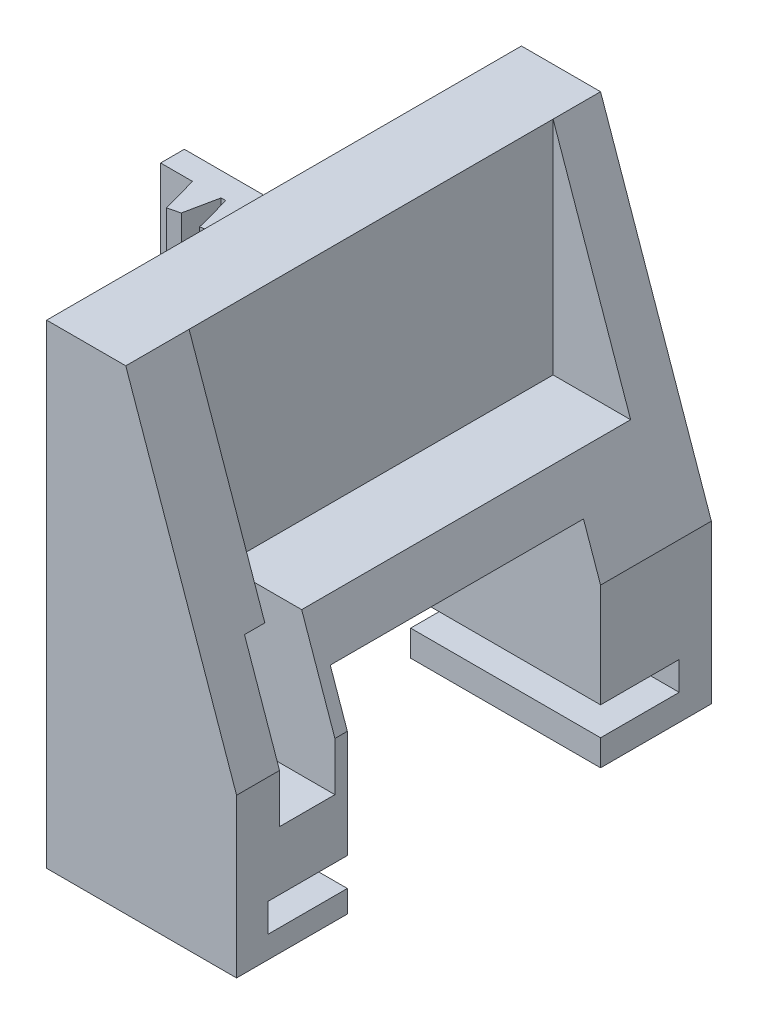
SolidWorks part; units mm, degrees
ref_plane "Front Plane" through (0, 0, 0) normal (0, 0, 1) x (1, 0, 0)
ref_plane "Top Plane" through (0, 0, 0) normal (0, 1, 0) x (1, 0, 0)
ref_plane "Right Plane" through (0, 0, 0) normal (1, 0, 0) x (0, 0, -1)
sketch "Sketch1" plane through (0, 0, 0) normal (0, 0, 1) x (1, 0, 0)
  line L0 (0, 0) -> (0, -30)
  line L1 (0, -30) -> (12, -30)
  line L2 (12, -30) -> (12, -20)
  line L3 (12, -20) -> (5, 0)
  line L4 (5, 0) -> (0, 0)
  dimension "D1" = 30
  dimension "D2" = 12
  dimension "D3" = 10
  dimension "D4" = 5
extrude "Boss-Extrude1" add sketch "Sketch1" against normal blind 30
sketch "Sketch4" plane through (0, 0, 0) normal (-1, 0, 0) x (0, 0, 1)
  line L0 (-30, 0) -> (-30, -30) construction
  line L1 (-23, -16.9179) -> (-7, -16.9179)
  line L2 (-23, -16.9179) -> (-23, -30.9179)
  line L3 (-23, -30.9179) -> (-7, -30.9179)
  line L4 (-7, -16.9179) -> (-7, -30.9179)
  point P4 (-23, -23.9179)
  dimension "D1" = 16
  dimension "D2" = 14
  dimension "D3" = 7
extrude "Cut-Extrude2" cut sketch "Sketch4" against normal blind 25 contours L2 L1 L4 L3
sketch "Sketch5" plane through (0, 0, 0) normal (-1, 0, 0) x (0, 0, 1)
  line L0 (-7, -16.9179) -> (-7, -30) construction
  line L1 (-7, -26.8) -> (-2, -26.8)
  line L2 (-7, -26.8) -> (-7, -28.6)
  line L3 (-7, -28.6) -> (-2, -28.6)
  line L4 (-2, -26.8) -> (-2, -28.6)
  line L5 (-7, -30) -> (0, -30) construction
  dimension "D1" = 1.8
  dimension "D2" = 5
  dimension "D3" = 1.4
extrude "Cut-Extrude3" cut sketch "Sketch5" against normal blind 15
ref_plane "Plane1" through (0, 0, -15.5) normal (0, 0, 1) x (1, 0, 0)
sketch "Sketch6" plane through (0, 0, -15.5) normal (0, 0, 1) x (1, 0, 0)
  line L0 (5, 0) -> (5, -14)
  line L1 (5, -14) -> (9.9, -14)
  line L2 (12, -20) -> (5, 0) construction
  line L3 (9.9, -14) -> (5, 0)
  dimension "D1" = 14
extrude "Cut-Extrude4" cut sketch "Sketch6" against normal mid plane 23
ref_plane "Plane2" through (0, -22, 0) normal (0, 1, 0) x (1, 0, 0)
sketch "Sketch7" plane through (0, -22, 0) normal (0, 1, 0) x (1, 0, 0)
  line L0 (0, 27.7) -> (-19, 27.7)
  line L1 (0, 30) -> (0, 0) construction
  line L3 (0, 27.7) -> (0, 26.2)
  line L4 (0, 26.2) -> (-0.5, 26.2)
  line L47 (-0.5, 26.2) -> (-0.9304, 24.1151)
  line L62 (-6.6, 15.5) -> (6.6, 15.5) construction
  line L108 (-19, 26.2) -> (-19, 27.7)
  line L112 (-0.9304, 24.1151) -> (-1.6865, 23.9276)
  line L113 (-2.3144, 26.2) -> (-2.597, 26.2)
  line L114 (-3.0274, 24.1151) -> (-3.7835, 23.9276)
  line L115 (-2.597, 26.2) -> (-3.0274, 24.1151)
  line L116 (-5.1244, 24.1151) -> (-5.8805, 23.9276)
  line L117 (-4.694, 26.2) -> (-5.1244, 24.1151)
  line L118 (-7.2214, 24.1151) -> (-7.9775, 23.9276)
  line L119 (-6.791, 26.2) -> (-7.2214, 24.1151)
  line L120 (-9.3184, 24.1151) -> (-10.0745, 23.9276)
  line L121 (-8.888, 26.2) -> (-9.3184, 24.1151)
  line L122 (-11.4154, 24.1151) -> (-12.1715, 23.9276)
  line L123 (-10.985, 26.2) -> (-11.4154, 24.1151)
  line L124 (-13.5124, 24.1151) -> (-14.2685, 23.9276)
  line L125 (-13.082, 26.2) -> (-13.5124, 24.1151)
  line L126 (-4.4114, 26.2) -> (-4.694, 26.2)
  line L127 (-6.5085, 26.2) -> (-6.791, 26.2)
  line L128 (-8.6055, 26.2) -> (-8.888, 26.2)
  line L129 (-10.7025, 26.2) -> (-10.985, 26.2)
  line L130 (-12.7995, 26.2) -> (-13.082, 26.2)
  line L132 (-15.6094, 24.1151) -> (-16.3655, 23.9276)
  line L133 (-15.179, 26.2) -> (-15.6094, 24.1151)
  line L134 (-14.8965, 26.2) -> (-15.179, 26.2)
  line L135 (-16.9935, 26.2) -> (-19, 26.2)
  arc A0 (-1.6865, 23.9276) -> (-2.3144, 26.2) centre (-44.8671, 13.2176) ccw
  arc A1 (-3.7835, 23.9276) -> (-4.4114, 26.2) centre (-46.9641, 13.2176) ccw
  arc A2 (-5.8805, 23.9276) -> (-6.5085, 26.2) centre (-49.0611, 13.2176) ccw
  arc A3 (-7.9775, 23.9276) -> (-8.6055, 26.2) centre (-51.1581, 13.2176) ccw
  arc A4 (-10.0745, 23.9276) -> (-10.7025, 26.2) centre (-53.2551, 13.2176) ccw
  arc A5 (-12.1715, 23.9276) -> (-12.7995, 26.2) centre (-55.3521, 13.2176) ccw
  arc A6 (-14.2685, 23.9276) -> (-14.8965, 26.2) centre (-57.4491, 13.2176) ccw
  arc A7 (-16.3655, 23.9276) -> (-16.9935, 26.2) centre (-59.5461, 13.2176) ccw
  dimension "D1" = 7
  dimension "D4" = 8
  dimension "D2" = 19
  dimension "D3" = 1.5
  dimension "D6" = 0.5
  dimension "D7" = 12.2
extrude "Boss-Extrude2" add sketch "Sketch7" along normal blind 8
sketch "Sketch8" plane through (0, 0, 0) normal (-1, 0, 0) x (0, 0, 1)
  line L0 (-6.2141, -13.6747) -> (-2.7141, -13.6747)
  line L6 (-2.7141, -13.6747) -> (-2.7141, -23.0747)
  line L7 (-2.7141, -23.0747) -> (-6.2141, -23.0747)
  line L9 (-6.2141, -23.0747) -> (-6.2141, -13.6747)
  point P2 (0, 0)
  point P5 (0, 0)
  dimension "D1" = 3.5
  dimension "D2" = 9.4
extrude "Cut-Extrude5" cut sketch "Sketch8" against normal through all
sketch "Sketch9" plane through (0, 0, 0) normal (-1, 0, 0) x (0, 0, 1)
  line L1 (-27.9704, -26.5537) -> (-22.9704, -26.5537)
  line L2 (-27.9704, -26.5537) -> (-27.9704, -28.3537)
  line L3 (-27.9704, -28.3537) -> (-22.9704, -28.3537)
  line L4 (-22.9704, -26.5537) -> (-22.9704, -28.3537)
  dimension "D1" = 1.8
  dimension "D2" = 5
extrude "Cut-Extrude6" cut sketch "Sketch9" against normal through all
